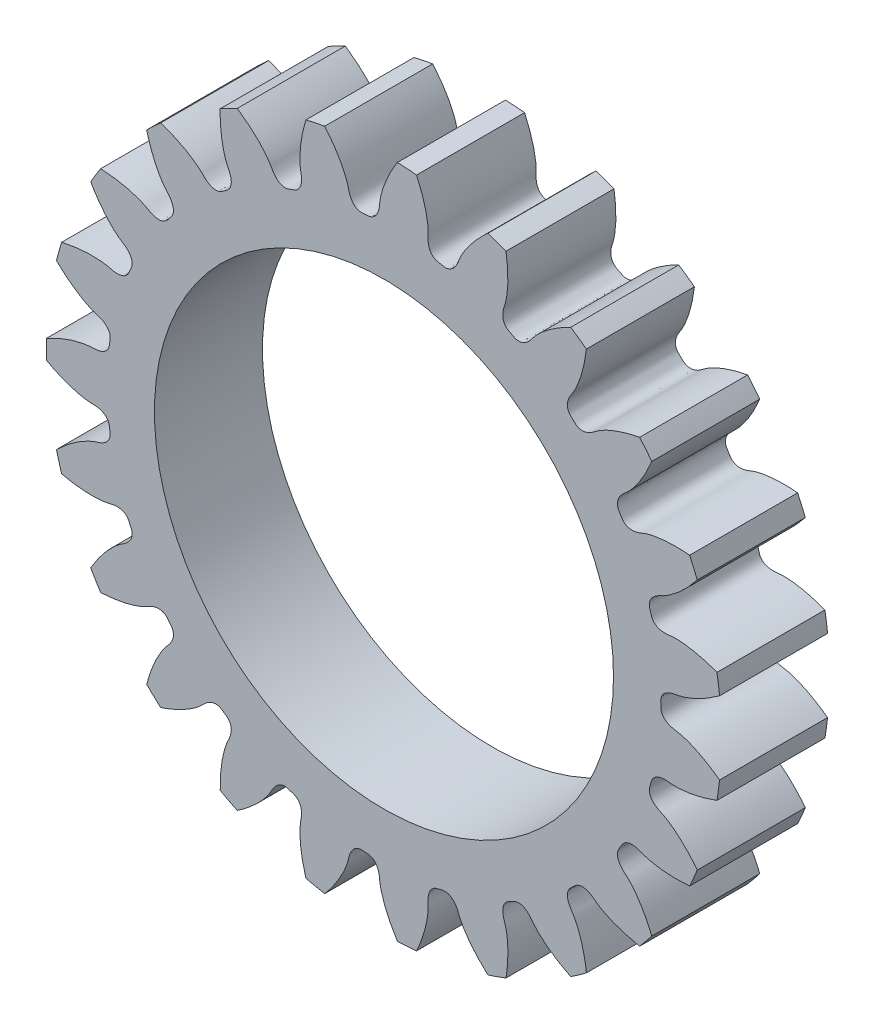
SolidWorks part; units mm, degrees
ref_plane "Front Plane" through (0, 0, 0) normal (0, 0, 1) x (1, 0, 0)
ref_plane "Top Plane" through (0, 0, 0) normal (0, 1, 0) x (1, 0, 0)
ref_plane "Right Plane" through (0, 0, 0) normal (1, 0, 0) x (0, 0, -1)
ref_axis "Axis1" through (0, 0, 55) along (0, 0, -1)
sketch "SketchRevolveSpurGear" plane through (0, 0, 0) normal (1, 0, 0) x (0, 0, -1)
  line L0 (0, 0) -> (1, 0) construction
  line L1 (-2, 0) -> (-2, 12.5)
  line L2 (-2, 12.5) -> (2, 12.5)
  line L3 (2, 12.5) -> (2, 0)
  line L4 (2, 0) -> (-2, 0)
  dimension "Side1" = 2
  dimension "OutsideRadius" = 12.5
  dimension "Side2" = 2
revolve "SpurGear" add sketch "SketchRevolveSpurGear" angle 360 about L0
sketch "SketchToothSpurGear" plane through (0, 0, 0) normal (0, 0, 1) x (1, 0, 0)
  arc A0 (12.4735, 1.3838) -> (12.4735, -1.3838) centre (0, 0) cw
  spline S0 degree 3 poles (12.4735, -1.3838) (12.378, -1.3122) (12.2357, -1.2115) (12.0454, -1.0893) (11.9121, -1.0093) (11.7848, -0.9378) (11.6637, -0.8745) (11.5493, -0.8188) (11.442, -0.7705) (11.3419, -0.7289) (11.2494, -0.6937) (11.1649, -0.6643) (11.0885, -0.6402) (11.0205, -0.621) (10.9611, -0.6061) (10.9105, -0.5949) (10.8141, -0.5768) (10.7159, -0.5642) (10.6184, -0.5348) (10.5693, -0.5171) (10.522, -0.4963) (10.4761, -0.472) (10.4314, -0.4431) (10.3878, -0.4082) (10.3457, -0.3655) (10.3068, -0.3128) (10.2742, -0.2484) (10.2548, -0.1781) (10.2469, -0.0939) (10.2519, 0) (10.2469, 0.0939) (10.2548, 0.1781) (10.2742, 0.2484) (10.3068, 0.3128) (10.3457, 0.3655) (10.3878, 0.4082) (10.4314, 0.4431) (10.4761, 0.472) (10.522, 0.4963) (10.5693, 0.5171) (10.6184, 0.5348) (10.7159, 0.5642) (10.8141, 0.5768) (10.9105, 0.5949) (10.9611, 0.6061) (11.0205, 0.621) (11.0885, 0.6402) (11.1649, 0.6643) (11.2494, 0.6937) (11.3419, 0.7289) (11.442, 0.7705) (11.5493, 0.8188) (11.6637, 0.8745) (11.7848, 0.9378) (11.9121, 1.0093) (12.0454, 1.0893) (12.2357, 1.2115) (12.378, 1.3122) (12.4735, 1.3838) knots 0 0 0 0 0.064534 0.094254 0.122275 0.148598 0.173223 0.19615 0.217378 0.236908 0.25474 0.270873 0.285308 0.298045 0.309084 0.318425 0.326067 0.362141 0.371724 0.381093 0.390355 0.399647 0.409152 0.419102 0.429779 0.441478 0.454421 0.468592 0.480659 0.5 0.519341 0.531408 0.545579 0.558522 0.570221 0.580898 0.590848 0.600353 0.609645 0.618907 0.628276 0.637859 0.673933 0.681575 0.690916 0.701955 0.714692 0.729127 0.74526 0.763092 0.782622 0.80385 0.826777 0.851402 0.877725 0.905746 0.935466 1 1 1 1
extrude "ToothExtrudeCutSpurGear" cut sketch "SketchToothSpurGear" against normal blind 2 and the other way blind 2
pattern_circular "PatternSpurGear" count 23 every 15.652 about axis through (0, 0, 55) along (0, 0, -1) of "ToothExtrudeCutSpurGear"
sketch "BoreRevolveSketch" plane through (0, 0, 0) normal (1, 0, 0) x (0, 0, -1)
  line L0 (0, 0) -> (1, 0) construction
  line L1 (-2, 0) -> (2, 0)
  line L2 (2, 0) -> (2, 8.5)
  line L3 (2, 8.5) -> (-2, 8.5)
  line L4 (-2, 8.5) -> (-2, 0)
  dimension "BoreSide1" = 2
  dimension "TaperSide1" = 8.5
  dimension "BoreSide2" = 2
  dimension "TaperSide2" = 8.5
revolve "BoreRevolveCut" cut sketch "BoreRevolveSketch" angle 360 about L0
sketch "AuxiliarySketchSpurGear" plane through (0, 0, 0) normal (0, 0, 1) x (1, 0, 0)
  circle A0 centre (0, 0) radius 11.5 construction
  circle A1 centre (0, 0) radius 10.8065 construction
  circle A2 centre (0, 0) radius 10.8403 construction
  circle A3 centre (0, 0) radius 12.5 construction
  circle A4 centre (0, 0) radius 10.25 construction
  dimension "PitchDiameter" = 23
  dimension "BaseDiameter" = 21.6129
  dimension "FormDiameter" = 21.6806
  dimension "MajorDiameter" = 25
  dimension "MinorDiameter" = 20.5
